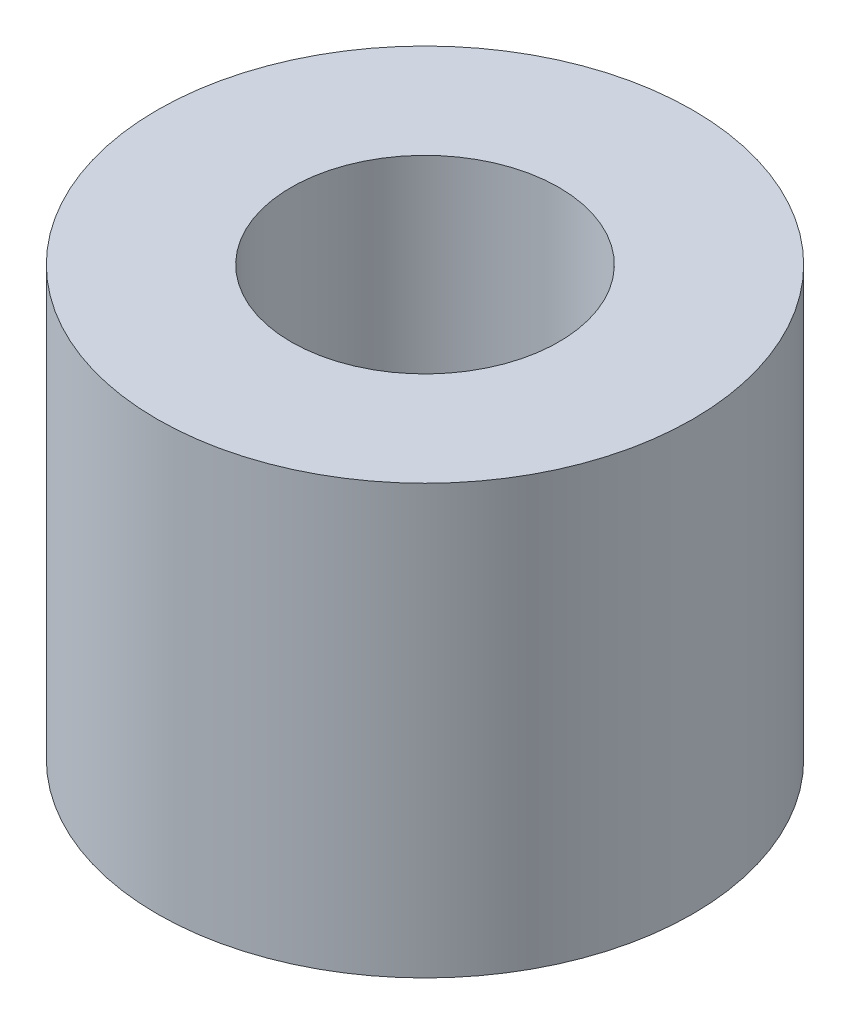
SolidWorks part; units mm, degrees
material "Brass"
ref_plane "Front Plane" through (0, 0, 0) normal (0, 0, 1) x (1, 0, 0)
ref_plane "Top Plane" through (0, 0, 0) normal (0, 1, 0) x (1, 0, 0)
ref_plane "Right Plane" through (0, 0, 0) normal (1, 0, 0) x (0, 0, -1)
sketch "Sketch1" plane through (0, 0, 0) normal (0, 1, 0) x (1, 0, 0)
  circle A0 centre (0, 0) radius 2.5
  dimension "D1" = 5
extrude "Boss-Extrude1" add sketch "Sketch1" along normal blind 4
hole_wizard "M3x0.5 Tapped Hole1" positions "Sketch2" profile "Sketch3" tap size "M3x0.5" standard "ANSI Metric" end condition through all
sketch "Sketch2" plane through (0, 4, 0) normal (0, 1, 0) x (1, 0, 0)
  point P0 (0, 0)
sketch "Sketch3" plane through (0, 4, 0) normal (1, 0, 0) x (0, 0, 1)
  line L0 (0, 0) -> (0, 4)
  line L1 (0, 4) -> (1.25, 4)
  line L2 (1.25, 4) -> (1.25, 0)
  line L5 (1.25, 0) -> (0, 0)
  line L11 (0, -6.35) -> (0, 107.95) construction
  dimension "Thru Tap Drill Dia." = 2.5
  dimension "Thru Tap Drill Depth" = 4
cosmetic thread "Hole Thread1"
